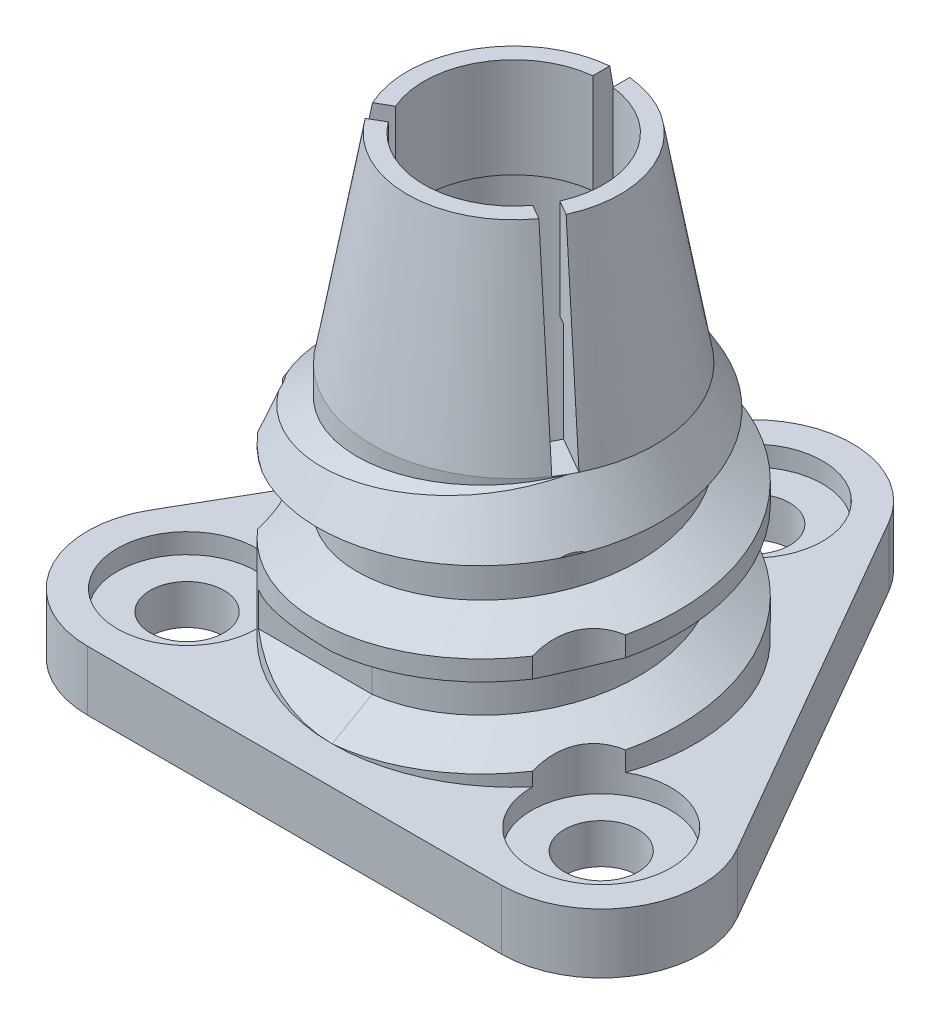
SolidWorks part; units mm, degrees
ref_plane "Front Plane" through (0, 0, 0) normal (0, 0, 1) x (1, 0, 0)
ref_plane "Top Plane" through (0, 0, 0) normal (0, 1, 0) x (1, 0, 0)
ref_plane "Right Plane" through (0, 0, 0) normal (1, 0, 0) x (0, 0, -1)
sketch "Sketch1" plane through (0, 0, 0) normal (0, 1, 0) x (1, 0, 0)
  line L0 (4.3301, 14.5) -> (14.7224, -3.5)
  line L1 (10.3923, -11) -> (-10.3923, -11)
  line L2 (-14.7224, -3.5) -> (-4.3301, 14.5)
  circle A0 centre (0, 0) radius 5.5
  circle A1 centre (0, 12) radius 1.85
  arc A2 (4.3301, 14.5) -> (-4.3301, 14.5) centre (0, 12) ccw
  circle A3 centre (10.3923, -6) radius 1.85
  arc A4 (10.3923, -11) -> (14.7224, -3.5) centre (10.3923, -6) ccw
  circle A5 centre (-10.3923, -6) radius 1.85
  arc A6 (-14.7224, -3.5) -> (-10.3923, -11) centre (-10.3923, -6) ccw
  dimension "D1" = 11
  dimension "D3" = 3.7
  dimension "D4" = 10
  dimension "D2" = 12
  dimension "D5" = 3
extrude "Boss-Extrude1" add sketch "Sketch1" along normal blind 3
sketch "Sketch2" plane through (0, 3, 0) normal (0, 1, 0) x (1, 0, 0)
  circle A0 centre (0, 0) radius 9.1073
extrude "Boss-Extrude2" add sketch "Sketch2" along normal blind 12
sketch "Sketch7" plane through (0, 15, 0) normal (0, 1, 0) x (1, 0, 0)
  circle A0 centre (0, 0) radius 7.1073
extrude "Cut-Extrude2" cut sketch "Sketch7" against normal blind 10 draft 30 flip side to cut
sketch "Sketch3" plane through (0, 15, 0) normal (0, 1, 0) x (1, 0, 0)
  circle A0 centre (0, 0) radius 7.1073
  circle A2 centre (0, 0) radius 9.1073 construction
  dimension "D1" = 2
extrude "Boss-Extrude3" add sketch "Sketch3" along normal blind 10 draft 10
sketch "Sketch4" plane through (0, 25, 0) normal (0, 1, 0) x (1, 0, 0)
  circle A0 centre (0, 0) radius 9.1073 construction
  circle A1 centre (0, 0) radius 9.1073
curve "Helix/Spiral1" pitch 5 height 20 radius 9.1073 centre (0, 25, 0) axis (0, -1, 0) start towards (0, 0, 1)
sketch "Sketch5" plane through (0, 0, 0) normal (1, 0, 0) x (0, 0, -1)
  line L0 (-9.1073, 25) -> (-7.1073, 25) construction
  line L1 (-7.1073, 25.8453) -> (-7.1073, 24.1547)
  line L2 (-7.1073, 24.1547) -> (-9.1073, 23)
  line L4 (-9.1073, 23) -> (-9.1073, 27)
  line L5 (-7.1073, 25.8453) -> (-9.1073, 27)
  spline S1 degree 3 poles (-9.1073, 25) (-9.1073, 24.8965) (-8.6331, 24.6872) (-6.6075, 24.3751) (-3.5759, 24.0625) (0, 23.75) (3.5759, 23.4375) (6.6075, 23.125) (8.6331, 22.8125) (9.3444, 22.5) (8.6331, 22.1875) (6.6075, 21.875) (2.5654, 21.4583) (-2.5654, 21.0417) (-6.6075, 20.625) (-8.6331, 20.3125) (-9.3444, 20) (-8.6331, 19.6875) (-6.6075, 19.375) (-2.5654, 18.9583) (2.5654, 18.5417) (6.6075, 18.125) (8.6331, 17.8125) (9.3444, 17.5) (8.6331, 17.1875) (6.6075, 16.875) (2.5654, 16.4583) (-2.5654, 16.0417) (-6.6075, 15.625) (-8.6331, 15.3125) (-9.3444, 15) (-8.6331, 14.6875) (-6.6075, 14.375) (-2.5654, 13.9583) (2.5654, 13.5417) (6.6075, 13.125) (8.6331, 12.8125) (9.3444, 12.5) (8.6331, 12.1875) (6.6075, 11.875) (2.5654, 11.4583) (-2.5654, 11.0417) (-6.6075, 10.625) (-8.6331, 10.3125) (-9.3444, 10) (-8.6331, 9.6875) (-6.6075, 9.375) (-2.5654, 8.9583) (2.5654, 8.5417) (6.6075, 8.125) (8.6331, 7.8125) (9.3444, 7.5) (8.6331, 7.1875) (6.6075, 6.875) (3.5759, 6.5625) (0, 6.25) (-3.5759, 5.9375) (-6.6075, 5.6249) (-8.6331, 5.3128) (-9.1073, 5.1035) (-9.1073, 5) knots 0 0 0 0 0.015625 0.03125 0.046875 0.0625 0.078125 0.09375 0.109375 0.125 0.140625 0.15625 0.171875 0.203125 0.21875 0.234375 0.25 0.265625 0.28125 0.296875 0.328125 0.34375 0.359375 0.375 0.390625 0.40625 0.421875 0.453125 0.46875 0.484375 0.5 0.515625 0.53125 0.546875 0.578125 0.59375 0.609375 0.625 0.640625 0.65625 0.671875 0.703125 0.71875 0.734375 0.75 0.765625 0.78125 0.796875 0.828125 0.84375 0.859375 0.875 0.890625 0.90625 0.921875 0.9375 0.953125 0.96875 0.984375 1 1 1 1 construction
  dimension "D1" = 30
  dimension "D2" = 4
  dimension "D3" = 2
sweep "Cut-Sweep1" cut profiles "Sketch5" path "Helix/Spiral1" align with end faces yes
sketch "Sketch6" plane through (0, 25, 0) normal (0, 1, 0) x (1, 0, 0)
  circle A0 centre (0, 0) radius 4.5
  dimension "D1" = 9
extrude "Cut-Extrude1" cut sketch "Sketch6" against normal through all
sketch "Sketch8" plane through (0, 0, 0) normal (1, 0, 0) x (0, 0, -1)
  line L4 (-7.1073, 4.1547) -> (-7.1073, 5.8453)
  line L5 (-7.1073, 5.8453) -> (-9.1073, 7)
  line L6 (-9.1073, 7) -> (-9.1073, 3)
  line L7 (-9.1073, 3) -> (-7.1073, 4.1547)
  line L8 (-7.1073, 4.1547) -> (-7.1073, 5.8453)
  line L9 (-7.1073, 5.8453) -> (-9.1073, 7)
  line L10 (-9.1073, 7) -> (-9.1073, 3)
  line L11 (-9.1073, 3) -> (-7.1073, 4.1547)
  dimension "D1" = 0
extrude "Cut-Extrude3" cut sketch "Sketch8" against normal blind 10
sketch "Sketch9" plane through (0, 25, 0) normal (0, 1, 0) x (1, 0, 0)
  line L0 (0, 0) -> (0, 15.6633) construction
  line L1 (0.5, 14.5042) -> (-0.5, 14.5042)
  line L2 (-0.5, 14.5042) -> (-0.5, 1.911)
  line L3 (-0.5, 1.911) -> (0.5, 1.911)
  line L4 (0.5, 14.5042) -> (0.5, 1.911)
  line L5 (12.811, -6.8191) -> (1.905, -0.5225)
  line L6 (12.311, -7.6851) -> (12.811, -6.8191)
  line L7 (12.311, -7.6851) -> (1.405, -1.3885)
  line L8 (1.905, -0.5225) -> (1.405, -1.3885)
  line L9 (-12.311, -7.6851) -> (-1.405, -1.3885)
  line L10 (-12.811, -6.8191) -> (-12.311, -7.6851)
  line L11 (-12.811, -6.8191) -> (-1.905, -0.5225)
  line L12 (-1.405, -1.3885) -> (-1.905, -0.5225)
  point P8 (0, 1.911)
  point P9 (0, 14.5042)
  dimension "D1" = 1
  dimension "D2" = 3
extrude "Cut-Extrude5" cut sketch "Sketch9" against normal up to vertex (51.9989 mm away) up to point (6.2089, 15, 3.4587)
sketch "Sketch10" plane through (0, 0, 0) normal (0, -1, 0) x (1, 0, 0)
  circle A0 centre (0, 0) radius 5
  dimension "D1" = 10
extrude "Cut-Extrude6" cut sketch "Sketch10" against normal offset from surface (20 mm away) 5 up to face at (0, 25, 3.9016)
sketch "Sketch11" plane through (0, 3, 0) normal (0, 1, 0) x (1, 0, 0)
  circle A0 centre (0, 12) radius 3.5
  circle A1 centre (10.3923, -6) radius 3.5
  circle A2 centre (-10.3923, -6) radius 3.5
  dimension "D1" = 7
extrude "Cut-Extrude7" cut sketch "Sketch11" against normal blind 1 and the other way through all
